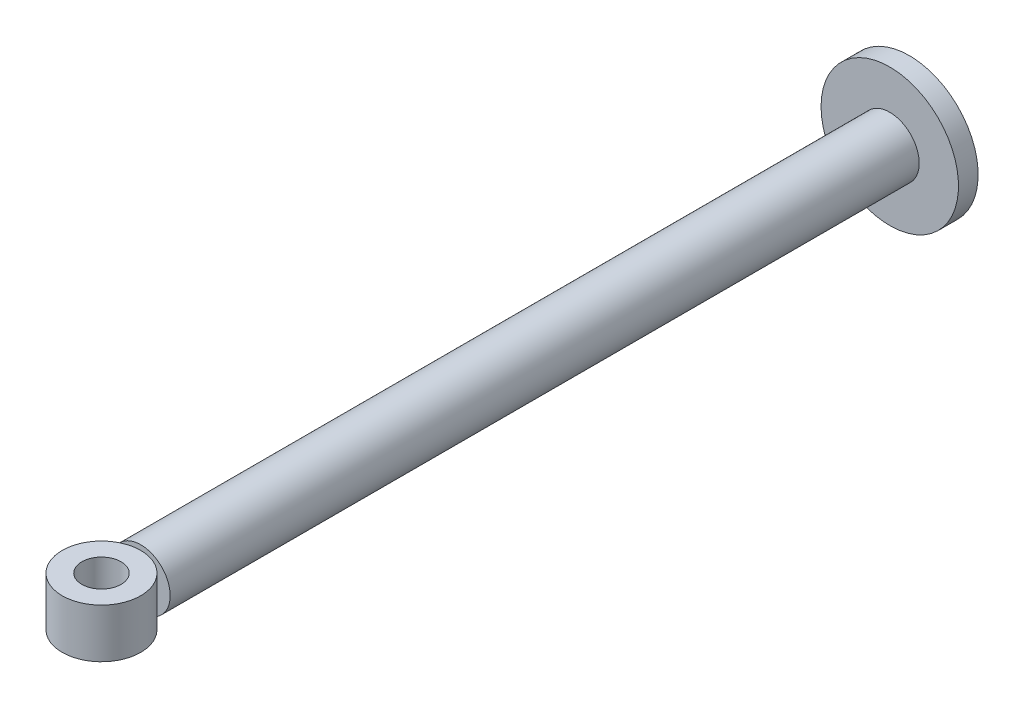
SolidWorks part; units mm, degrees
ref_plane "Front Plane" through (0, 0, 0) normal (0, 0, 1) x (1, 0, 0)
ref_plane "Top Plane" through (0, 0, 0) normal (0, 1, 0) x (1, 0, 0)
ref_plane "Right Plane" through (0, 0, 0) normal (1, 0, 0) x (0, 0, -1)
sketch "Sketch1" plane through (0, 0, 0) normal (0, 0, 1) x (1, 0, 0)
  circle A0 centre (0, 0) radius 3
  dimension "D1" = 6
extrude "Boss-Extrude1" add sketch "Sketch1" along normal blind 78.3
sketch "Sketch2" plane through (0, 0, 0) normal (0, 1, 0) x (1, 0, 0)
  line L0 (0, -78.3) -> (0, -82.3) construction
  line L1 (-3, -78.3) -> (3, -78.3) construction
  circle A0 centre (0, -82.3) radius 2
  circle A1 centre (0, -82.3) radius 4
  dimension "D1" = 8
  dimension "D2" = 4
extrude "Boss-Extrude2" add sketch "Sketch2" along normal blind 2.5 and the other way blind 2.5
sketch "Sketch3" plane through (0, 0, 0) normal (0, 0, -1) x (-1, 0, 0)
  circle A0 centre (0, 0) radius 7
  circle A1 centre (0, 0) radius 3 construction
  dimension "D1" = 4
extrude "Boss-Extrude3" add sketch "Sketch3" against normal blind 2
